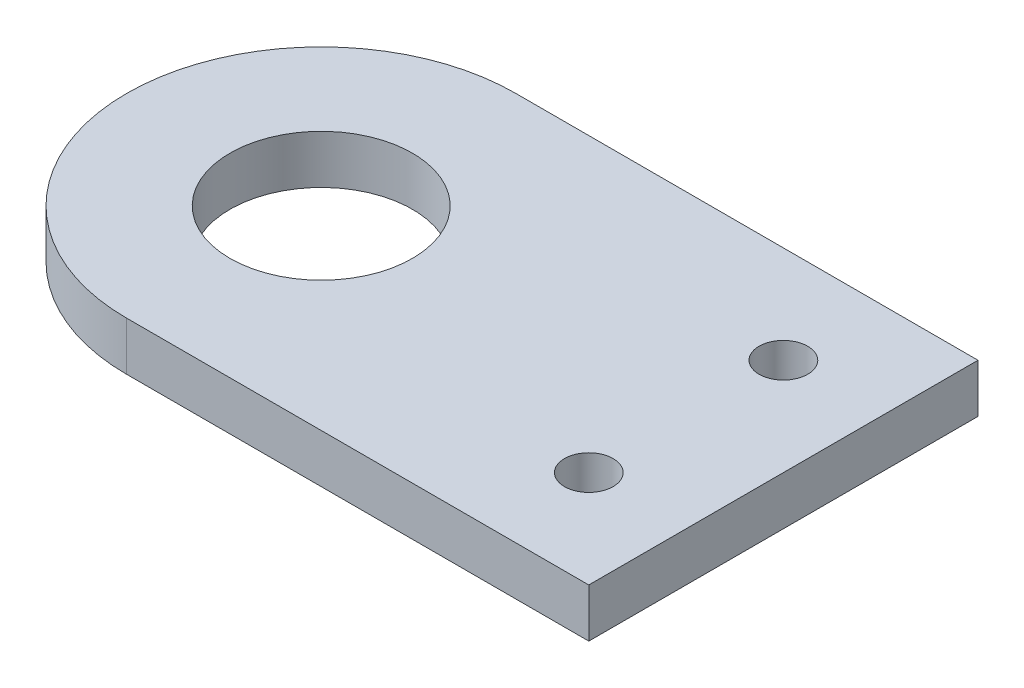
SolidWorks part; units mm, degrees
ref_plane "Front" through (0, 0, 0) normal (0, 0, 1) x (1, 0, 0)
ref_plane "Top" through (0, 0, 0) normal (0, 1, 0) x (1, 0, 0)
ref_plane "Right" through (0, 0, 0) normal (1, 0, 0) x (0, 0, -1)
sketch "Sketch1" plane through (0, 0, 0) normal (0, 1, 0) x (1, 0, 0)
  line L0 (0, 16) -> (38, 16)
  line L1 (38, 16) -> (38, -16)
  line L2 (38, -16) -> (0, -16)
  circle A0 centre (0, 0) radius 16
  circle A1 centre (0, 0) radius 7.5
  dimension "D1" = 38
extrude "Boss-Extrude1" add sketch "Sketch1" along normal blind 4 contours A0 A1 | A0 L2 L1 L0 region at (25.0325, 0, 0) region at (10.9937, 0, -10.9937)
sketch "Sketch2" plane through (0, 4, 0) normal (0, 1, 0) x (1, 0, 0)
  line L0 (38, 0) -> (30, 0)
  line L1 (38, 16) -> (38, -16) construction
  line L2 (30, 0) -> (30, 8)
  line L3 (30, 8) -> (30, -8)
  circle A0 centre (30, -8) radius 2
  circle A1 centre (30, 8) radius 2
  dimension "D1" = 8
  dimension "D2" = 8
  dimension "D3" = 30
extrude "Cut-Extrude1" cut sketch "Sketch2" against normal through all contours A0 | A1 region at (28.6258, 4, -9.3742) region at (31.3742, 4, 6.6258)
sketch "Sketch3" plane through (0, 4, 0) normal (0, 1, 0) x (1, 0, 0)
  circle A0 centre (0, 0) radius 7.5
  circle A1 centre (0, 0) radius 16
extrude "Boss-Extrude2" [suppressed] add sketch "Sketch3" along normal blind 2
